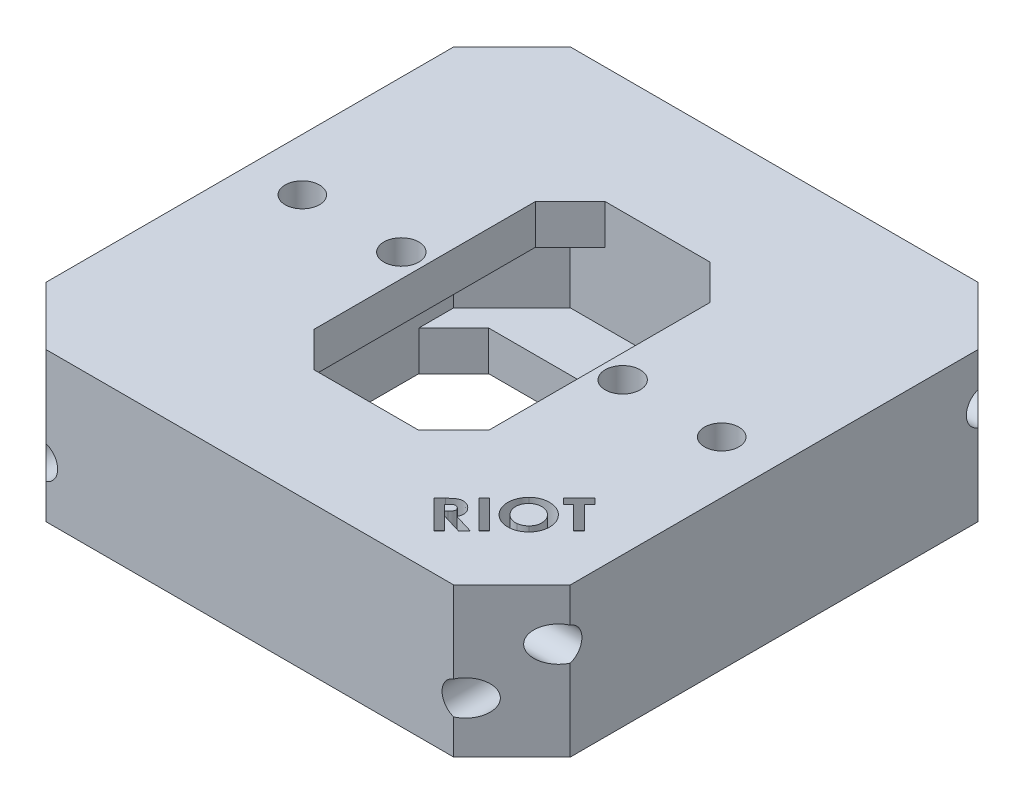
SolidWorks part; units mm, degrees
ref_plane "정면" through (0, 0, 0) normal (0, 0, 1) x (1, 0, 0)
ref_plane "윗면" through (0, 0, 0) normal (0, 1, 0) x (1, 0, 0)
ref_plane "우측면" through (0, 0, 0) normal (1, 0, 0) x (0, 0, -1)
sketch "스케치1" plane through (0, 0, 0) normal (1, 0, 0) x (0, 0, -1)
  line L0 (0, 5) -> (0, -5) construction
  line L1 (-22.5, -5) -> (22.5, -5)
  line L2 (-22.5, -5) -> (-22.5, 5)
  line L3 (-22.5, 5) -> (22.5, 5)
  line L4 (22.5, -5) -> (22.5, 5)
  line L5 (-22.5, -5) -> (22.5, 5) construction
  line L6 (-22.5, 5) -> (22.5, -5) construction
  circle A0 centre (-18, 2) radius 1.5
  circle A1 centre (18, 2) radius 1.5
  point P0 (0, 0)
  dimension "D3" = 3
  dimension "D1" = 45
  dimension "D2" = 10
  dimension "D4" = 36
  dimension "D5" = 3
extrude "보스-돌출1" add sketch "스케치1" along normal blind 45
sketch "스케치2" plane through (0, 0, 22.5) normal (0, 0, 1) x (1, 0, 0)
  line L0 (22.5, 5) -> (22.5, -5) construction
  line L1 (0, -5) -> (45, -5)
  line L2 (0, -5) -> (0, 5)
  line L3 (0, 5) -> (45, 5)
  line L4 (45, -5) -> (45, 5)
  line L5 (0, -5) -> (45, 5) construction
  line L6 (0, 5) -> (45, -5) construction
  line L7 (45, 5) -> (45, -5) construction
  circle A0 centre (4.5, -2) radius 1.5
  circle A1 centre (40.5, -2) radius 1.5
  point P0 (22.5, 0)
  dimension "D3" = 3
  dimension "D1" = 45
  dimension "D2" = 10
  dimension "D4" = 36
  dimension "D5" = 7
extrude "컷-돌출1" cut sketch "스케치2" against normal blind 45 contours A0 | A1 region at (4.5, -2, 22.5) region at (40.5, -2, 22.5)
chamfer "모따기1" distance 5 angle 45 4 edges at (0, 0, 22.5) (0, 0, -22.5) (45, 0, -22.5) (45, 0, 22.5)
sketch "스케치4" plane through (0, -5, 0) normal (0, -1, 0) x (1, 0, 0)
  line L0 (0, 0) -> (45, 0) construction
  line L1 (45, 17.5) -> (45, -17.5) construction
  line L3 (10, 12.5) -> (35, 12.5)
  line L4 (10, 12.5) -> (10, -12.5)
  line L5 (10, -12.5) -> (35, -12.5)
  line L6 (35, 12.5) -> (35, -12.5)
  line L7 (10, 12.5) -> (35, -12.5) construction
  line L8 (10, -12.5) -> (35, 12.5) construction
  point P5 (22.5, 0)
  dimension "D1" = 25
extrude "컷-돌출3" cut sketch "스케치4" against normal through all
chamfer "모따기2" distance 5 angle 45 4 edges at (35, 0, -12.5) (10, 0, -12.5) (10, 0, 12.5) (35, 0, 12.5)
sketch "스케치5" plane through (0, 5, 0) normal (0, 1, 0) x (1, 0, 0)
  line L0 (10, 7.5) -> (15, 12.5) construction
  line L1 (15, 12.5) -> (30, 12.5) construction
  line L2 (10, -7.5) -> (10, 7.5) construction
  line L3 (15, -12.5) -> (10, -7.5) construction
  line L4 (30, -12.5) -> (15, -12.5) construction
  line L5 (35, -7.5) -> (30, -12.5) construction
  line L6 (35, 7.5) -> (35, -7.5) construction
  line L7 (30, 12.5) -> (35, 7.5) construction
  line L8 (10, 7.5) -> (15, 12.5)
  line L9 (15, 12.5) -> (30, 12.5)
  line L10 (10, -7.5) -> (10, 7.5)
  line L11 (15, -12.5) -> (10, -7.5)
  line L12 (30, -12.5) -> (15, -12.5)
  line L13 (35, -7.5) -> (30, -12.5)
  line L14 (35, 7.5) -> (35, -7.5)
  line L15 (30, 12.5) -> (35, 7.5)
  line L16 (22.5, 12.5) -> (22.5, -12.5) construction
  line L23 (10, 0) -> (35, 0) construction
  line L28 (15, 12.5) -> (15, -12.5)
  line L29 (30, 12.5) -> (30, -12.5)
  circle A5 centre (13, 0) radius 1.5
  circle A6 centre (32, 0) radius 1.5
  point P12 (10, 0)
  point P21 (35, 0)
  point P23 (22.5, 0)
  point P43 (22.5, 0)
  dimension "D4" = 3
extrude "보스-돌출2" add sketch "스케치5" against normal blind 2 contours L10 A5 | L14 A6 region at (12.6803, 5, -9.8197) region at (32.3197, 5, -9.8197)
sketch "스케치14" plane through (0, -5, 0) normal (0, -1, 0) x (1, 0, 0)
  line L0 (15, 12.5) -> (10, 7.5) construction
  line L1 (30, 12.5) -> (15, 12.5) construction
  line L2 (10, 7.5) -> (10, -7.5) construction
  line L3 (10, -7.5) -> (15, -12.5) construction
  line L4 (15, -12.5) -> (30, -12.5) construction
  line L5 (30, -12.5) -> (35, -7.5) construction
  line L6 (35, -7.5) -> (35, 7.5) construction
  line L7 (30, 12.5) -> (35, 7.5) construction
  line L8 (15, 12.5) -> (10, 7.5)
  line L9 (30, 12.5) -> (15, 12.5)
  line L10 (10, 7.5) -> (10, -7.5)
  line L11 (10, -7.5) -> (15, -12.5)
  line L12 (15, -12.5) -> (30, -12.5)
  line L13 (30, -12.5) -> (35, -7.5)
  line L14 (35, -7.5) -> (35, 7.5)
  line L15 (30, 12.5) -> (35, 7.5)
  line L16 (10, 7.5) -> (35, 7.5)
  line L17 (10, -7.5) -> (35, -7.5)
  line L18 (22.5, 12.5) -> (22.5, -12.5) construction
  circle A0 centre (13, 0) radius 1.5 construction
  circle A1 centre (13, 0) radius 1.5
  circle A2 centre (22.5, 9.5) radius 1.5
  circle A3 centre (22.5, -9.5) radius 1.5
  line M8 (15, 12.5) -> (30, 12.5)
  line M9 (30, 12.5) -> (35, 7.5)
  line M11 (35, -7.5) -> (30, -12.5)
  line M12 (30, -12.5) -> (15, -12.5)
  line M13 (15, -12.5) -> (10, -7.5)
  line M15 (10, 7.5) -> (15, 12.5)
  dimension "D3" = 3
  dimension "D1" = 3
  dimension "D2" = 3
extrude "보스-돌출3" add sketch "스케치14" against normal blind 2 contours L18 L16 A2 M8 M15 | L9 L18 A2 L16 M9 | L18 L17 L12 A3 M13 | L17 L18 A3 M12 M11 region at (17.056, -5, 9.8139) region at (27.944, -5, 9.8139) region at (17.056, -5, -9.8139) region at (27.944, -5, -9.8139)
chamfer "모따기3" distance 3 angle 45 8 edges at (10, -4, 7.5) (10, -4, -7.5) (35, -4, -7.5) (35, -4, 7.5) (30, 4, -12.5) (15, 4, -12.5) (15, 4, 12.5) (30, 4, 12.5)
sketch "스케치7" plane through (0, 5, 0) normal (0, 1, 0) x (1, 0, 0)
  line L0 (32, -22.5) -> (45, -9.5) construction
  line L1 (45, 17.5) -> (45, -17.5) construction
  line L2 (40, -22.5) -> (5, -22.5) construction
  text T0 "<b>RIOT</b>"
  dimension "D1" = 45
  dimension "D2" = 8
extrude "컷-돌출4" cut sketch "스케치7" against normal blind 1
sketch "스케치12" plane through (0, 5, 0) normal (0, 1, 0) x (1, 0, 0)
  line L0 (0, 0) -> (45, 0) construction
  line L1 (45, 17.5) -> (45, -17.5) construction
  line L2 (22.5, 22.5) -> (22.5, -22.5) construction
  line L3 (40, 22.5) -> (5, 22.5) construction
  line L4 (40, -22.5) -> (5, -22.5) construction
  circle A0 centre (5, 0) radius 1.5
  circle A1 centre (40, 0) radius 1.5
  circle A2 centre (22.5, -17.5) radius 1.5
  circle A3 centre (22.5, 17.5) radius 1.5
  dimension "D1" = 3
  dimension "D3" = 3
  dimension "D2" = 35
  dimension "D4" = 35
extrude "컷-돌출5" cut sketch "스케치12" along normal blind 7 from surface contours A2 | A3 region at (22.5, 5, 17.5) region at (22.5, 5, -17.5) starting at face at (22.5, -5, 0)
sketch "스케치16" plane through (0, 5, 0) normal (0, 1, 0) x (1, 0, 0)
  line L0 (22.5, 22.5) -> (22.5, -22.5) construction
  line L1 (40, 22.5) -> (5, 22.5) construction
  line L2 (40, -22.5) -> (5, -22.5) construction
  line L3 (0, 0) -> (45, 0) construction
  line L4 (0, 17.5) -> (0, -17.5) construction
  line L5 (45, 17.5) -> (45, -17.5) construction
  line L14 (15, 9.5) -> (15, -9.5)
  line L15 (18, 12.5) -> (15, 9.5)
  line L16 (27, 12.5) -> (18, 12.5)
  line L17 (30, 9.5) -> (27, 12.5)
  line L18 (30, -9.5) -> (30, 9.5)
  line L19 (27, -12.5) -> (30, -9.5)
  line L20 (18, -12.5) -> (27, -12.5)
  line L21 (15, -9.5) -> (18, -12.5)
  line L22 (15, 9.5) -> (15, -9.5)
  line L23 (18, 12.5) -> (15, 9.5)
  line L24 (27, 12.5) -> (18, 12.5)
  line L25 (30, 9.5) -> (27, 12.5)
  line L26 (30, -9.5) -> (30, 9.5)
  line L27 (27, -12.5) -> (30, -9.5)
  line L28 (18, -12.5) -> (27, -12.5)
  line L29 (15, -9.5) -> (18, -12.5)
  line L30 (0, 17.5) -> (0, -17.5)
  line L31 (0, -17.5) -> (5, -22.5)
  line L32 (5, -22.5) -> (40, -22.5)
  line L33 (40, -22.5) -> (45, -17.5)
  line L34 (45, -17.5) -> (45, 17.5)
  line L35 (45, 17.5) -> (40, 22.5)
  line L36 (40, 22.5) -> (5, 22.5)
  line L37 (5, 22.5) -> (0, 17.5)
  line L38 (0, 17.5) -> (0, -17.5)
  line L39 (0, -17.5) -> (5, -22.5)
  line L40 (5, -22.5) -> (40, -22.5)
  line L41 (40, -22.5) -> (45, -17.5)
  line L42 (45, -17.5) -> (45, 17.5)
  line L43 (45, 17.5) -> (40, 22.5)
  line L44 (40, 22.5) -> (5, 22.5)
  line L45 (5, 22.5) -> (0, 17.5)
  circle A0 centre (4.5, 0) radius 1.475
  circle A1 centre (40.5, 0) radius 1.475
  circle A2 centre (4.5, 0) radius 2.75
  circle A3 centre (40.5, 0) radius 2.75
  circle A5 centre (13, 0) radius 1.5
  circle A6 centre (13, 0) radius 1.5
  circle A7 centre (32, 0) radius 1.5
  circle A8 centre (32, 0) radius 1.5
  spline M4 degree 3 poles (36.7204, -15.3285) (36.6919, -15.2989) (36.6355, -15.2403) (36.5585, -15.1466) (36.4881, -15.0498) (36.4249, -14.9493) (36.3687, -14.8453) (36.3193, -14.7379) (36.2783, -14.6266) (36.2429, -14.5128) (36.2159, -14.3967) (36.1962, -14.2801) (36.1839, -14.1633) (36.181, -14.0464) (36.1838, -13.9292) (36.1965, -13.8122) (36.2148, -13.6947) (36.2427, -13.5781) (36.2762, -13.4627) (36.319, -13.3515) (36.3663, -13.2433) (36.4221, -13.1399) (36.4837, -13.0395) (36.5535, -12.9441) (36.6282, -12.8511) (36.6839, -12.794) (36.712, -12.7652) knots 0 0 0 0 0.043163 0.085623 0.127549 0.169116 0.210504 0.251896 0.293387 0.335331 0.377281 0.418695 0.459747 0.500849 0.541705 0.583001 0.624618 0.666807 0.709151 0.750959 0.792148 0.83342 0.874518 0.9161 0.957711 1 1 1 1
  spline M5 degree 3 poles (36.712, -12.7652) (36.7555, -12.7235) (36.8415, -12.6414) (36.9838, -12.5364) (37.1322, -12.4466) (37.2881, -12.373) (37.4516, -12.317) (37.6221, -12.2769) (37.7996, -12.2533) (37.982, -12.2457) (38.1646, -12.2545) (38.3433, -12.2805) (38.5156, -12.3232) (38.6812, -12.3831) (38.84, -12.4601) (38.9919, -12.5541) (39.1382, -12.6642) (39.2277, -12.7493) (39.2732, -12.7925) knots 0 0 0 0 0.063416 0.125149 0.185768 0.245889 0.306295 0.367492 0.430083 0.49463 0.559445 0.622382 0.684529 0.746041 0.80758 0.870019 0.933968 1 1 1 1
  spline M6 degree 3 poles (39.2732, -12.7925) (39.3159, -12.8376) (39.4, -12.9263) (39.5095, -13.0709) (39.6028, -13.2215) (39.679, -13.3787) (39.7382, -13.5422) (39.7805, -13.7123) (39.8053, -13.8888) (39.8145, -14.0692) (39.8068, -14.2493) (39.7832, -14.425) (39.7424, -14.5942) (39.6846, -14.7567) (39.6108, -14.9127) (39.5193, -15.061) (39.4127, -15.204) (39.33, -15.2912) (39.2879, -15.3355) knots 0 0 0 0 0.065722 0.129505 0.19176 0.253108 0.3142 0.375693 0.438476 0.502685 0.56687 0.629094 0.690229 0.75092 0.811501 0.872735 0.935328 1 1 1 1
  spline M7 degree 3 poles (39.2879, -15.3355) (39.2418, -15.3795) (39.1513, -15.4657) (39.003, -15.5769) (38.8499, -15.6714) (38.6895, -15.747) (38.5238, -15.8056) (38.3514, -15.8456) (38.1731, -15.868) (37.9909, -15.8725) (37.8092, -15.8608) (37.6322, -15.8328) (37.4622, -15.7886) (37.2989, -15.7286) (37.1429, -15.6528) (36.9941, -15.5606) (36.8514, -15.4535) (36.7645, -15.3705) (36.7204, -15.3285) knots 0 0 0 0 0.066795 0.131017 0.19395 0.255242 0.316563 0.377983 0.440492 0.504736 0.568848 0.631149 0.692445 0.752779 0.813293 0.874042 0.936156 1 1 1 1
  line M8 (35.1466, -19.3534) -> (32.6969, -16.9037)
  line M9 (32.6969, -16.9037) -> (33.1919, -16.4087)
  spline M10 degree 3 poles (33.1919, -16.4087) (33.2246, -16.3762) (33.2877, -16.3138) (33.3819, -16.2268) (33.4706, -16.1488) (33.5547, -16.0808) (33.6334, -16.0222) (33.7068, -15.9728) (33.7755, -15.933) (33.8603, -15.8939) (33.9656, -15.8599) (34.0951, -15.8399) (34.2281, -15.8418) (34.3395, -15.8605) (34.4289, -15.8838) (34.4952, -15.9083) (34.5602, -15.9367) (34.6239, -15.9708) (34.6861, -16.0102) (34.7474, -16.0542) (34.8063, -16.1045) (34.8441, -16.1407) (34.8633, -16.1591) knots 0 0 0 0 0.071108 0.136909 0.1977 0.253313 0.303556 0.349038 0.389718 0.425841 0.492861 0.559584 0.626985 0.697081 0.733275 0.769302 0.805934 0.842696 0.880594 0.919308 0.958949 1 1 1 1
  spline M11 degree 3 poles (34.8633, -16.1591) (34.8828, -16.1791) (34.9211, -16.2185) (34.9719, -16.2814) (35.0182, -16.3441) (35.0567, -16.4093) (35.0896, -16.4752) (35.1176, -16.5418) (35.1374, -16.6102) (35.1527, -16.6792) (35.1607, -16.7495) (35.1638, -16.821) (35.1602, -16.8937) (35.1502, -16.9678) (35.1341, -17.0428) (35.111, -17.1189) (35.0836, -17.1968) (35.0603, -17.2479) (35.0484, -17.2739) knots 0 0 0 0 0.068856 0.135151 0.199091 0.260824 0.321353 0.380498 0.438808 0.496531 0.554539 0.612754 0.672721 0.73373 0.796763 0.861638 0.929591 1 1 1 1
  line M12 (35.0484, -17.2739) -> (36.7171, -17.7829)
  line M13 (36.7171, -17.7829) -> (36.2074, -18.2926)
  line M14 (36.2074, -18.2926) -> (34.6186, -17.806)
  line M15 (34.6186, -17.806) -> (34.5752, -17.8495)
  line M16 (34.5752, -17.8495) -> (35.6128, -18.8872)
  line M17 (35.6128, -18.8872) -> (35.1466, -19.3534)
  line M18 (15, -9.5) -> (15, 9.5)
  line M19 (15, 9.5) -> (18, 12.5)
  line M20 (18, 12.5) -> (27, 12.5)
  line M21 (27, 12.5) -> (30, 9.5)
  line M22 (30, 9.5) -> (30, -9.5)
  line M23 (30, -9.5) -> (27, -12.5)
  line M24 (27, -12.5) -> (18, -12.5)
  line M25 (18, -12.5) -> (15, -9.5)
  line M26 (0, 17.5) -> (0, -17.5)
  line M27 (0, -17.5) -> (5, -22.5)
  line M28 (5, -22.5) -> (40, -22.5)
  line M29 (40, -22.5) -> (45, -17.5)
  line M30 (45, -17.5) -> (45, 17.5)
  line M31 (45, 17.5) -> (40, 22.5)
  line M32 (40, 22.5) -> (5, 22.5)
  line M33 (5, 22.5) -> (0, 17.5)
  circle M34 centre (13, 0) radius 1.5
  circle M35 centre (32, 0) radius 1.5
  line M36 (37.081, -17.419) -> (34.6313, -14.9693)
  line M37 (34.6313, -14.9693) -> (35.094, -14.5065)
  line M38 (35.094, -14.5065) -> (37.5438, -16.9562)
  line M39 (37.5438, -16.9562) -> (37.081, -17.419)
  line M40 (38.7222, -11.7982) -> (38.2623, -11.3383)
  line M41 (38.2623, -11.3383) -> (39.6162, -9.9844)
  line M42 (39.6162, -9.9844) -> (40.0761, -10.4443)
  line M43 (40.0761, -10.4443) -> (39.6295, -10.891)
  line M44 (39.6295, -10.891) -> (41.6193, -12.8807)
  line M45 (41.6193, -12.8807) -> (41.1467, -13.3533)
  line M46 (41.1467, -13.3533) -> (39.1569, -11.3635)
  line M47 (39.1569, -11.3635) -> (38.7222, -11.7982)
  dimension "D2" = 2.95
  dimension "D3" = 5.5
  dimension "D1" = 36
  dimension "D4" = 0
  dimension "D5" = 0
  dimension "D6" = 0
  dimension "D7" = 0
extrude "컷-돌출6" cut sketch "스케치16" against normal blind 7 contours A0 | A1 region at (4.5, 5, 0) region at (40.5, 5, 0)
extrude "보스-돌출4" add sketch "스케치16<3>" along normal blind 1.4 contours A2 A0 | M33 M26 M27 M28 M29 M30 M31 M32 M34 M39 M36 M37 M38 M47 M40 M41 M42 M43 M44 M45 M46 M35 M25 M18 M19 M20 M21 M22 M23 M24 M17 M8 M9 M10 M11 M12 M13 M14 M15 M16 M7 M4 M5 M6 | A3 A1 region at (2.95, 5, -19.55) region at (1.8278, 5, 0) region at (37.8278, 5, 0)
sketch "스케치16<3>" plane through (0, 5, 0) normal (0, 1, 0) x (1, 0, 0) same geometry as "스케치16"
sketch "스케치17" plane through (0, -5, 0) normal (0, -1, 0) x (1, 0, 0)
  line L0 (0, 0) -> (45, 0) construction
  line L1 (0, 17.5) -> (0, -17.5) construction
  line L2 (45, 17.5) -> (45, -17.5) construction
  line L3 (22.5, 22.5) -> (22.5, -22.5) construction
  line L4 (40, 22.5) -> (5, 22.5) construction
  line L5 (40, -22.5) -> (5, -22.5) construction
  line L6 (13, -7.5) -> (32, -7.5) construction
  line L7 (35, -4.5) -> (32, -7.5) construction
  line L8 (35, -4.5) -> (35, 4.5) construction
  line L9 (32, 7.5) -> (35, 4.5) construction
  line L10 (13, 7.5) -> (32, 7.5) construction
  line L11 (10, 4.5) -> (13, 7.5) construction
  line L12 (10, 4.5) -> (10, -4.5) construction
  line L13 (13, -7.5) -> (10, -4.5) construction
  line L14 (40, 22.5) -> (5, 22.5)
  line L15 (5, 22.5) -> (0, 17.5)
  line L16 (0, 17.5) -> (0, -17.5)
  line L17 (0, -17.5) -> (5, -22.5)
  line L18 (5, -22.5) -> (40, -22.5)
  line L19 (40, -22.5) -> (45, -17.5)
  line L20 (45, -17.5) -> (45, 17.5)
  line L21 (45, 17.5) -> (40, 22.5)
  line L22 (40, 22.5) -> (5, 22.5)
  line L23 (5, 22.5) -> (0, 17.5)
  line L24 (0, 17.5) -> (0, -17.5)
  line L25 (0, -17.5) -> (5, -22.5)
  line L26 (5, -22.5) -> (40, -22.5)
  line L27 (40, -22.5) -> (45, -17.5)
  line L28 (45, -17.5) -> (45, 17.5)
  line L29 (45, 17.5) -> (40, 22.5)
  line L30 (13, -7.5) -> (32, -7.5)
  line L31 (35, -4.5) -> (32, -7.5)
  line L32 (35, -4.5) -> (35, 4.5)
  line L33 (32, 7.5) -> (35, 4.5)
  line L34 (13, 7.5) -> (32, 7.5)
  line L35 (10, 4.5) -> (13, 7.5)
  line L36 (10, 4.5) -> (10, -4.5)
  line L37 (13, -7.5) -> (10, -4.5)
  circle A0 centre (22.5, 17.5) radius 2.75
  circle A1 centre (22.5, -17.5) radius 2.75
  circle A2 centre (22.5, 17.5) radius 1.5
  circle A3 centre (22.5, -17.5) radius 1.5
  circle A4 centre (22.5, 9.5) radius 1.5 construction
  circle A5 centre (22.5, -9.5) radius 1.5 construction
  circle A6 centre (22.5, 9.5) radius 1.5
  circle A7 centre (22.5, -9.5) radius 1.5
  circle M2 centre (22.5, -17.5) radius 1.5
  circle M3 centre (22.5, 17.5) radius 1.5
  line M4 (32, -7.5) -> (13, -7.5)
  line M5 (13, -7.5) -> (10, -4.5)
  line M6 (10, -4.5) -> (10, 4.5)
  line M7 (10, 4.5) -> (13, 7.5)
  line M8 (13, 7.5) -> (32, 7.5)
  line M9 (32, 7.5) -> (35, 4.5)
  line M10 (35, 4.5) -> (35, -4.5)
  line M11 (35, -4.5) -> (32, -7.5)
  line M12 (40, 22.5) -> (5, 22.5)
  line M13 (5, 22.5) -> (0, 17.5)
  line M14 (0, 17.5) -> (0, -17.5)
  line M15 (0, -17.5) -> (5, -22.5)
  line M16 (5, -22.5) -> (40, -22.5)
  line M17 (40, -22.5) -> (45, -17.5)
  line M18 (45, -17.5) -> (45, 17.5)
  line M19 (45, 17.5) -> (40, 22.5)
  circle M20 centre (22.5, 9.5) radius 1.5
  circle M21 centre (22.5, -9.5) radius 1.5
  dimension "D1" = 5.5
  dimension "D2" = 0
extrude "보스-돌출5" add sketch "스케치17" along normal blind 1.4 contours A0 A1 M19 M12 M13 M14 M15 M16 M17 M18 M11 M4 M5 M6 M7 M8 M9 M10 M21 M20 | A0 M3 | A1 M2 region at (42.05, -5, 19.55) region at (19.8278, -5, 17.5) region at (19.8278, -5, -17.5)
sketch "스케치18" plane through (0, 5, 0) normal (0, 1, 0) x (1, 0, 0)
  line L0 (33.6195, -16.8939) -> (34.1208, -17.3952) construction
  line L1 (34.1208, -17.3952) -> (34.2674, -17.2487) construction
  line L2 (33.7478, -16.7656) -> (33.6195, -16.8939) construction
  line L3 (33.6195, -16.8939) -> (34.1208, -17.3952)
  line L4 (34.1208, -17.3952) -> (34.2674, -17.2487)
  line L5 (33.7478, -16.7656) -> (33.6195, -16.8939)
  spline S0 degree 3 poles (2036.7834, 2224.3986) (27.6639, -39.5086) (42.3306, -15.9492) (38.6224, -13.1006) (38.5242, -13.0404) (38.4229, -12.9889) (38.3167, -12.9498) (38.2064, -12.9219) (38.0927, -12.9033) (37.9762, -12.8968) (37.8603, -12.9) (37.7469, -12.9138) (37.6384, -12.9395) (37.5335, -12.9739) (37.4344, -13.0222) (37.3384, -13.0786) (33.8012, -15.743) (48.8505, -39.4638) (-1954.6931, 2229.7835) knots -7.470287 -7.470287 -7.470287 -7.470287 0.066576 0.130924 0.193675 0.255484 0.317313 0.379141 0.44213 0.506359 0.570501 0.632405 0.693495 0.753469 0.813401 0.874172 0.936135 8.067852 8.067852 8.067852 8.067852 only from (38.8034, -13.2553) to (37.1635, -13.2265) construction
  spline S1 degree 3 poles (-2226.6688, 1955.0472) (64.3534, -25.7036) (39.5774, -9.9535) (37.0142, -13.4029) (36.9549, -13.4979) (36.9082, -13.5979) (36.8715, -13.7015) (36.845, -13.809) (36.8308, -13.9207) (36.8265, -14.035) (36.8334, -14.1496) (36.8517, -14.2624) (36.881, -14.3719) (36.9223, -14.478) (36.9745, -14.5808) (37.0379, -14.6805) (39.9068, -18.4087) (64.1704, -3.2087) (-2203.1558, -2009.7492) knots -6.824198 -6.824198 -6.824198 -6.824198 0.064361 0.126566 0.187119 0.247113 0.306692 0.366467 0.427748 0.490454 0.553235 0.615172 0.676902 0.738352 0.800895 0.865133 0.93132 8.47687 8.47687 8.47687 8.47687 only from (37.1635, -13.2265) to (37.1986, -14.8672) construction
  spline S2 degree 3 poles (-1934.4458, -2275.7969) (49.8535, 14.0645) (33.5172, -12.1628) (37.4065, -15.0421) (37.5181, -15.1086) (37.6339, -15.1603) (37.7533, -15.197) (37.8763, -15.2193) (42.2613, -15.5363) (46.1072, 16.0869) (97.6265, -3014.5793) knots -13.620396 -13.620396 -13.620396 -13.620396 0.134919 0.264338 0.389625 0.511388 0.631323 0.751326 0.87369 13.348779 13.348779 13.348779 13.348779 only from (37.1986, -14.8672) to (38.1324, -15.2191) construction
  spline S3 degree 3 poles (503.2409, -2978.8037) (25.8926, 7.2849) (34.0602, -16.1313) (38.3307, -15.1843) (38.4246, -15.154) (38.5143, -15.1151) (38.6011, -15.0695) (38.6841, -15.0161) (42.0238, -12.3922) (28.3458, 9.2308) (2046.661, -2243.6663) knots -16.091627 -16.091627 -16.091627 -16.091627 0.128246 0.253753 0.376936 0.499713 0.622315 0.746008 0.871533 16.608144 16.608144 16.608144 16.608144 only from (38.1324, -15.2191) to (38.8364, -14.884) construction
  spline S4 degree 3 poles (2312.7369, -1971.5694) (11.4208, -1.9445) (36.5552, -18.043) (38.9817, -14.7107) (39.0393, -14.617) (39.0848, -14.5176) (39.1211, -14.4145) (39.1454, -14.3065) (39.1594, -14.1945) (39.1627, -14.0795) (39.1558, -13.964) (39.1386, -13.8507) (39.1094, -13.7414) (39.0702, -13.6358) (39.02, -13.534) (38.9586, -13.4366) (36.2093, -9.8247) (11.9084, -25.1412) (2286.6346, 1973.2564) knots -6.612921 -6.612921 -6.612921 -6.612921 0.063439 0.125024 0.185519 0.245153 0.305268 0.365906 0.42782 0.491597 0.555848 0.618796 0.68074 0.742599 0.804629 0.867983 0.932739 8.293298 8.293298 8.293298 8.293298 only from (38.8364, -14.884) to (38.8034, -13.2553) construction
  spline S5 degree 3 poles (2216.3827, -2075.8352) (15.2279, -10.9199) (31.5294, -20.3448) (34.3652, -17.1437) (34.4063, -17.0949) (34.4409, -17.0479) (34.4687, -17.0032) (34.4912, -16.9616) (34.5067, -16.9219) (34.5202, -16.8731) (34.5223, -16.8118) (34.5048, -16.7392) (33.0589, -14.2008) (5.8873, -32.3773) (2367.0079, 1869.6561) knots -16.643654 -16.643654 -16.643654 -16.643654 0.100081 0.19179 0.275868 0.35264 0.422443 0.484085 0.539733 0.590433 0.68392 0.779036 0.882524 12.101831 12.101831 12.101831 12.101831 only from (34.2674, -17.2487) to (34.4069, -16.6057) construction
  spline S6 degree 3 poles (1959.8095, 2283.8529) (23.0767, -37.5605) (36.3394, -17.892) (34.3233, -16.5401) (34.2762, -16.5196) (34.2271, -16.5071) (34.1772, -16.5021) (34.1273, -16.5049) (34.078, -16.5157) (34.037, -16.5308) (34.0036, -16.5489) (33.9748, -16.5661) (33.9442, -16.589) (33.9105, -16.6159) (33.8732, -16.6463) (33.8342, -16.6827) (30.8804, -19.3983) (39.1566, -33.8634) (-2045.235, 2145.938) knots -9.141317 -9.141317 -9.141317 -9.141317 0.070529 0.137752 0.202948 0.268313 0.332835 0.396244 0.460987 0.527672 0.564485 0.607914 0.657117 0.712484 0.77478 0.84328 0.918783 16.300882 16.300882 16.300882 16.300882 only from (34.4069, -16.6057) to (33.7478, -16.7656) construction
  spline S7 degree 3 poles (38.8034, -13.2553) (38.774, -13.2274) (38.7161, -13.1726) (38.6224, -13.1006) (38.5242, -13.0404) (38.4229, -12.9889) (38.3167, -12.9498) (38.2064, -12.9219) (38.0927, -12.9033) (37.9762, -12.8968) (37.8603, -12.9) (37.7469, -12.9138) (37.6384, -12.9395) (37.5335, -12.9739) (37.4344, -13.0222) (37.3384, -13.0786) (37.2474, -13.1471) (37.1918, -13.1998) (37.1635, -13.2265) knots 0 0 0 0 0.066576 0.130924 0.193675 0.255484 0.317313 0.379141 0.44213 0.506359 0.570501 0.632405 0.693495 0.753469 0.813401 0.874172 0.936135 1 1 1 1
  spline S8 degree 3 poles (37.1635, -13.2265) (37.1362, -13.255) (37.0826, -13.3109) (37.0142, -13.4029) (36.9549, -13.4979) (36.9082, -13.5979) (36.8715, -13.7015) (36.845, -13.809) (36.8308, -13.9207) (36.8265, -14.035) (36.8334, -14.1496) (36.8517, -14.2624) (36.881, -14.3719) (36.9223, -14.478) (36.9745, -14.5808) (37.0379, -14.6805) (37.1123, -14.7772) (37.1695, -14.8368) (37.1986, -14.8672) knots 0 0 0 0 0.064361 0.126566 0.187119 0.247113 0.306692 0.366467 0.427748 0.490454 0.553235 0.615172 0.676902 0.738352 0.800895 0.865133 0.93132 1 1 1 1
  spline S9 degree 3 poles (37.1986, -14.8672) (37.2323, -14.8992) (37.2983, -14.962) (37.4065, -15.0421) (37.5181, -15.1086) (37.6339, -15.1603) (37.7533, -15.197) (37.8763, -15.2193) (38.0034, -15.2285) (38.089, -15.2223) (38.1324, -15.2191) knots 0 0 0 0 0.134919 0.264338 0.389625 0.511388 0.631323 0.751326 0.87369 1 1 1 1
  spline S10 degree 3 poles (38.1324, -15.2191) (38.1662, -15.2147) (38.2329, -15.206) (38.3307, -15.1843) (38.4246, -15.154) (38.5143, -15.1151) (38.6011, -15.0695) (38.6841, -15.0161) (38.763, -14.9541) (38.8117, -14.9075) (38.8364, -14.884) knots 0 0 0 0 0.128246 0.253753 0.376936 0.499713 0.622315 0.746008 0.871533 1 1 1 1
  spline S11 degree 3 poles (38.8364, -14.884) (38.863, -14.8563) (38.9154, -14.8017) (38.9817, -14.7107) (39.0393, -14.617) (39.0848, -14.5176) (39.1211, -14.4145) (39.1454, -14.3065) (39.1594, -14.1945) (39.1627, -14.0795) (39.1558, -13.964) (39.1386, -13.8507) (39.1094, -13.7414) (39.0702, -13.6358) (39.02, -13.534) (38.9586, -13.4366) (38.8869, -13.3424) (38.8316, -13.2847) (38.8034, -13.2553) knots 0 0 0 0 0.063439 0.125024 0.185519 0.245153 0.305268 0.365906 0.42782 0.491597 0.555848 0.618796 0.68074 0.742599 0.804629 0.867983 0.932739 1 1 1 1
  spline S12 degree 3 poles (34.2674, -17.2487) (34.2851, -17.2306) (34.319, -17.1959) (34.3652, -17.1437) (34.4063, -17.0949) (34.4409, -17.0479) (34.4687, -17.0032) (34.4912, -16.9616) (34.5067, -16.9219) (34.5202, -16.8731) (34.5223, -16.8118) (34.5048, -16.7392) (34.4648, -16.6689) (34.427, -16.6276) (34.4069, -16.6057) knots 0 0 0 0 0.100081 0.19179 0.275868 0.35264 0.422443 0.484085 0.539733 0.590433 0.68392 0.779036 0.882524 1 1 1 1
  spline S13 degree 3 poles (34.4069, -16.6057) (34.3934, -16.5935) (34.367, -16.5695) (34.3233, -16.5401) (34.2762, -16.5196) (34.2271, -16.5071) (34.1772, -16.5021) (34.1273, -16.5049) (34.078, -16.5157) (34.037, -16.5308) (34.0036, -16.5489) (33.9748, -16.5661) (33.9442, -16.589) (33.9105, -16.6159) (33.8732, -16.6463) (33.8342, -16.6827) (33.7914, -16.7221) (33.7627, -16.7507) (33.7478, -16.7656) knots 0 0 0 0 0.070529 0.137752 0.202948 0.268313 0.332835 0.396244 0.460987 0.527672 0.564485 0.607914 0.657117 0.712484 0.77478 0.84328 0.918783 1 1 1 1
extrude "보스-돌출6" add sketch "스케치18" along normal up to vertex (1.4 mm away) up to point (34.6313, 6.4, 14.9693)
